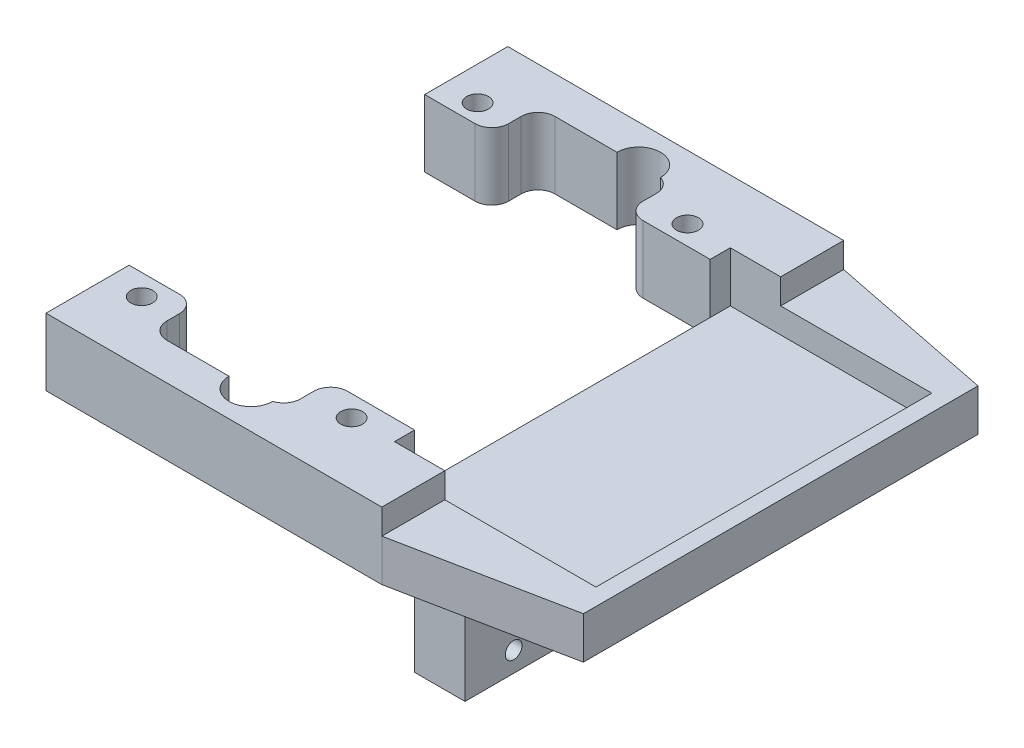
SolidWorks part; units mm, degrees
ref_plane "Front Plane" through (0, 0, 0) normal (0, 0, 1) x (1, 0, 0)
ref_plane "Top Plane" through (0, 0, 0) normal (0, 1, 0) x (1, 0, 0)
ref_plane "Right Plane" through (0, 0, 0) normal (1, 0, 0) x (0, 0, -1)
sketch "Sketch1" plane through (0, 0, 0) normal (0, 1, 0) x (1, 0, 0)
  line L0 (50.8, -0.508) -> (25.4, -5.588)
  line L1 (0, 0) -> (25.4, 0) construction
  line L2 (0, 0) -> (0, 58.674) construction
  line L3 (0, 58.674) -> (25.4, 58.674) construction
  line L4 (25.4, 0) -> (25.4, 58.674) construction
  line L5 (-25.4, 64.262) -> (25.4, 64.262)
  line L6 (-25.4, 64.262) -> (-25.4, -5.588)
  line L7 (-25.4, -5.588) -> (25.4, -5.588)
  line L8 (25.4, 64.262) -> (25.4, -5.588)
  line L9 (25.4, 59.182) -> (50.8, 59.182)
  line L10 (25.4, 59.182) -> (25.4, -0.508)
  line L11 (25.4, -0.508) -> (50.8, -0.508)
  line L12 (50.8, 59.182) -> (50.8, -0.508)
  line L13 (50.8, 59.182) -> (25.4, 64.262)
  circle A0 centre (0, 0) radius 3.302
  circle A1 centre (0, 58.674) radius 3.302
  circle A2 centre (11.43, 54.61) radius 1.651
  circle A3 centre (-20.32, 54.61) radius 1.651
  circle A4 centre (11.43, 3.81) radius 1.651
  circle A5 centre (-20.32, 54.61) radius 1.651
  circle A6 centre (-20.32, 3.81) radius 1.651
  circle A7 centre (11.43, 3.81) radius 1.651
  dimension "D1" = 6.604
  dimension "D3" = 6.604
  dimension "D11" = 11.43
  dimension "D12" = 4.064
  dimension "D17" = 3.302
  dimension "D2" = 58.674
  dimension "D4" = 25.4
  dimension "D5" = 69.85
  dimension "D6" = 5.588
  dimension "D7" = 50.8
  dimension "D8" = 25.4
  dimension "D9" = 59.69
  dimension "D10" = 5.08
  dimension "D13" = 2
  dimension "D14" = 2
  dimension "D15" = 2
  dimension "D16" = 2
extrude "Boss-Extrude1" add sketch "Sketch1" along normal blind 6.35 contours L8 L5 L6 L7 A1 A0 | L9 L13 L8 | L12 L9 L8 L11 | L11 L8 L0 region at (33.8667, 0, 2.2013) region at (38.1, 0, -29.337) region at (0.0442, 0, -29.3383) region at (33.8667, 0, -60.8753)
sketch "Sketch2" plane through (0, 6.35, 0) normal (0, 1, 0) x (1, 0, 0)
  line L0 (50.8, 59.182) -> (50.8, -0.508) construction
  line L5 (25.4, 64.262) -> (25.4, -5.588) construction
  line L6 (50.8, 59.182) -> (-25.4, 59.182) construction
  line L7 (-25.4, 64.262) -> (-25.4, -5.588) construction
  line L8 (50.8, -0.508) -> (-25.4, -0.508) construction
  line L9 (17.78, 54.737) -> (48.26, 54.737)
  line L14 (17.78, 54.737) -> (17.78, 3.937)
  line L15 (17.78, 3.937) -> (48.26, 3.937)
  line L16 (48.26, 54.737) -> (48.26, 3.937)
  dimension "D1" = 30.48
  dimension "D2" = 50.8
  dimension "D3" = 4.445
  dimension "D4" = 2.54
  dimension "D5" = 4.445
extrude "Cut-Extrude1" cut sketch "Sketch2" against normal blind 3.81
sketch "Sketch3" plane through (0, 6.35, 0) normal (0, 1, 0) x (1, 0, 0)
  line L0 (-25.4, 64.262) -> (-25.4, -5.588) construction
  line L1 (-25.4, 51.689) -> (17.78, 51.689)
  line L2 (-25.4, 51.689) -> (-25.4, 6.985)
  line L3 (-25.4, 6.985) -> (17.78, 6.985)
  line L4 (17.78, 51.689) -> (17.78, 6.985)
  line L5 (25.4, 64.262) -> (25.4, -5.588) construction
  line L7 (-25.4, 64.262) -> (25.4, 64.262) construction
  line L8 (-15.24, 51.689) -> (5.08, 51.689)
  line L9 (-15.24, 51.689) -> (-15.24, 58.674)
  line L10 (-15.24, 58.674) -> (5.08, 58.674)
  line L11 (5.08, 51.689) -> (5.08, 58.674)
  line L12 (-15.24, 6.985) -> (5.08, 6.985)
  line L13 (-15.24, 6.985) -> (-15.24, 0)
  line L14 (-15.24, 0) -> (5.08, 0)
  line L15 (5.08, 6.985) -> (5.08, 0)
  line M5 (17.78, 3.937) -> (17.78, 54.737)
  line M13 (-25.4, 64.262) -> (-25.4, -5.588)
  circle M15 centre (0, 58.674) radius 3.302
  circle M16 centre (0, 0) radius 3.302
  dimension "D1" = 44.704
  dimension "D2" = 12.573
  dimension "D3" = 10.16
  dimension "D4" = 20.32
  dimension "D5" = 58.674
  dimension "D6" = 6.985
  dimension "D7" = 6.985
  dimension "D8" = 7.62
extrude "Cut-Extrude2" cut sketch "Sketch3" against normal through all contours L1 L11 L10 L9 M15 | L3 L1 M13 M5 | L15 L3 L13 L14 M16 region at (-3.81, 6.35, -29.337) region at (-5.7771, 6.35, -54.8946) region at (-5.7771, 6.35, -3.7794)
sketch "Sketch13" plane through (0, 6.35, 0) normal (0, 1, 0) x (1, 0, 0)
  line L1 (-25.4, 51.689) -> (25.4, 51.689)
  line L2 (-25.4, 51.689) -> (-25.4, 64.262)
  line L3 (-25.4, 64.262) -> (25.4, 64.262)
  line L4 (25.4, 51.689) -> (25.4, 64.262)
  line L5 (-25.4, 6.985) -> (25.4, 6.985)
  line L6 (-25.4, 6.985) -> (-25.4, -5.588)
  line L7 (-25.4, -5.588) -> (25.4, -5.588)
  line L8 (25.4, 6.985) -> (25.4, -5.588)
  line L9 (17.78, 54.737) -> (25.4, 54.737)
  line L10 (17.78, 54.737) -> (17.78, 51.689)
  line L11 (17.78, 51.689) -> (25.4, 51.689)
  line L12 (25.4, 54.737) -> (25.4, 51.689)
  line L13 (17.78, 3.937) -> (25.4, 3.937)
  line L14 (17.78, 3.937) -> (17.78, 6.985)
  line L15 (17.78, 6.985) -> (25.4, 6.985)
  line L16 (25.4, 3.937) -> (25.4, 6.985)
  circle M1 centre (-20.32, 3.81) radius 1.651
  circle M2 centre (11.43, 3.81) radius 1.651
  circle M3 centre (-20.32, 54.61) radius 1.651
  circle M4 centre (11.43, 54.61) radius 1.651
  arc M5 (-3.302, 58.674) -> (3.302, 58.674) centre (0, 58.674) cw
  line M6 (3.302, 58.674) -> (5.08, 58.674)
  line M7 (5.08, 58.674) -> (5.08, 51.689)
  line M8 (5.08, 51.689) -> (17.78, 51.689)
  line M9 (17.78, 51.689) -> (17.78, 54.737)
  line M10 (17.78, 54.737) -> (48.26, 54.737)
  line M12 (48.26, 3.937) -> (17.78, 3.937)
  line M13 (17.78, 3.937) -> (17.78, 6.985)
  line M14 (17.78, 6.985) -> (5.08, 6.985)
  line M15 (5.08, 6.985) -> (5.08, 0)
  line M16 (5.08, 0) -> (3.302, 0)
  arc M17 (3.302, 0) -> (-3.302, 0) centre (0, 0) cw
  line M18 (-3.302, 0) -> (-15.24, 0)
  line M19 (-15.24, 0) -> (-15.24, 6.985)
  line M20 (-15.24, 6.985) -> (-25.4, 6.985)
  line M21 (-25.4, 6.985) -> (-25.4, -5.588)
  line M22 (-25.4, -5.588) -> (25.4, -5.588)
  line M26 (25.4, 64.262) -> (-25.4, 64.262)
  line M27 (-25.4, 64.262) -> (-25.4, 51.689)
  line M28 (-25.4, 51.689) -> (-15.24, 51.689)
  line M29 (-15.24, 51.689) -> (-15.24, 58.674)
  line M30 (-15.24, 58.674) -> (-3.302, 58.674)
extrude "Boss-Extrude7" add sketch "Sketch13" along normal blind 3.81 contours L4 M10 M26 M27 M28 M29 M30 M5 M6 M7 M8 M9 M3 M4 | L8 M12 M13 M14 M15 M16 M17 M18 M19 M20 M21 M22 M2 M1 region at (-24.8767, 6.35, -57.9755) region at (-20.32, 6.35, -6.4617)
sketch "Sketch15" plane through (0, 0, 0) normal (0, -1, 0) x (1, 0, 0)
  line L0 (25.4, 5.588) -> (25.4, -64.262) construction
  line L1 (5.08, -6.985) -> (17.78, -6.985) construction
  line L2 (17.78, -6.985) -> (25.4, -6.985)
  line L3 (17.78, -6.985) -> (17.78, -51.689)
  line L4 (17.78, -51.689) -> (25.4, -51.689)
  line L5 (25.4, -6.985) -> (25.4, -51.689)
  line L6 (5.08, -51.689) -> (17.78, -51.689) construction
  dimension "D1" = 44.704
extrude "Boss-Extrude8" add sketch "Sketch15" along normal blind 21.59
sketch "Sketch16" plane through (17.78, 0, 0) normal (-1, 0, 0) x (0, 0, 1)
  line L0 (-6.985, -21.59) -> (-51.689, -21.59) construction
  line L1 (-51.689, -21.59) -> (-51.689, 0) construction
  circle A0 centre (-44.323, -18.542) radius 1.27
  circle A1 centre (-34.671, -18.542) radius 1.27
  circle A2 centre (-24.003, -18.542) radius 1.27
  circle A3 centre (-14.351, -18.542) radius 1.27
  dimension "D1" = 2.54
  dimension "D2" = 3.048
  dimension "D7" = 7.366
  dimension "D3" = 2
  dimension "D4" = 2
  dimension "D5" = 2
extrude "Cut-Extrude3" cut sketch "Sketch16" against normal through all
fillet "Fillet1" radius 2.54 8 edges at (-15.24, 5.08, -6.985) (-15.24, 5.08, 0) (5.08, 5.08, 0) (5.08, 5.08, -6.985) (5.08, 5.08, -51.689) (-15.24, 5.08, -51.689) (-15.24, 5.08, -58.674) (5.08, 5.08, -58.674)
chamfer "Chamfer2" distance 2.54 angle 45 3 edges at (21.59, 0, -51.689) (21.59, 0, -6.985) (25.4, 0, -29.337)
